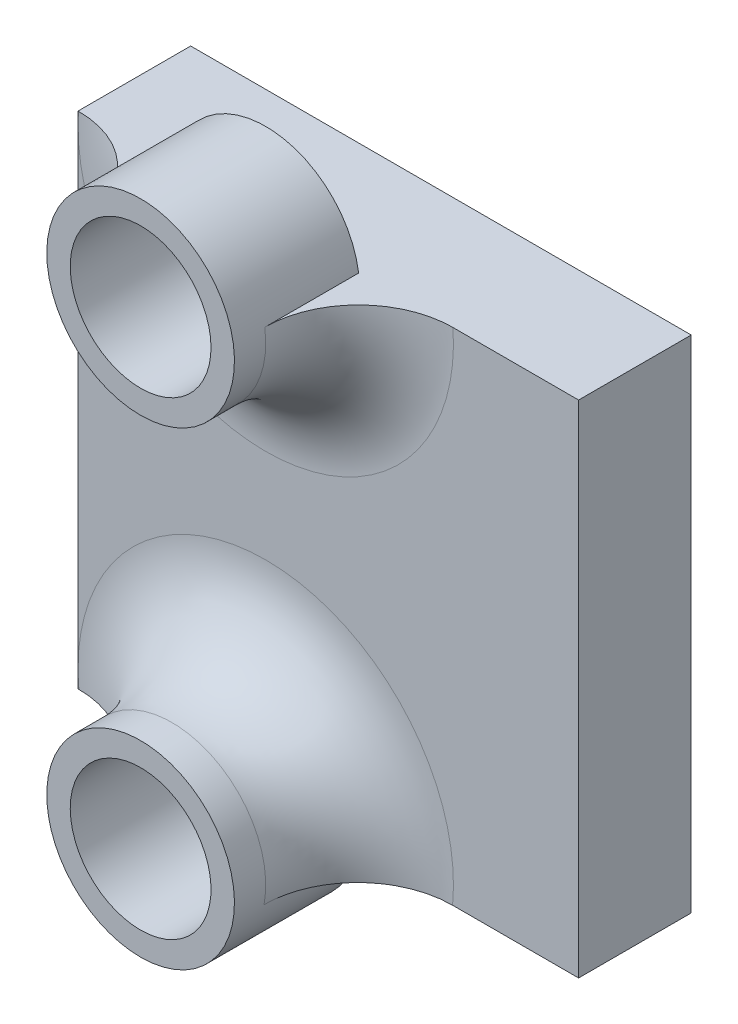
SolidWorks part; units mm, degrees
ref_plane "Front Plane" through (0, 0, 0) normal (0, 0, 1) x (1, 0, 0)
ref_plane "Top Plane" through (0, 0, 0) normal (0, 1, 0) x (1, 0, 0)
ref_plane "Right Plane" through (0, 0, 0) normal (1, 0, 0) x (0, 0, -1)
sketch "Sketch5" plane through (0, 0, 9.6) normal (0, 0, 1) x (1, 0, 0)
  line L0 (-72, -8) -> (-56, -8)
  line L1 (-72, -8) -> (-72, -24)
  line L2 (-56, -8) -> (-56, -24)
  line L4 (-72, -24) -> (-56, -24)
  line L5 (-56, -24) -> (-56, 8)
  line L6 (-56, 8) -> (-72, 8)
  line L7 (-72, 8) -> (-72, -24)
  line L8 (-72, -24) -> (-56, -24)
  arc A0 (-67.55, -23.425) -> (-64.45, -23.425) centre (-66, -23.425) ccw construction
  arc A1 (-67.55, -8.425) -> (-64.45, -8.425) centre (-66, -8.425) ccw construction
  arc A2 (-67.55, -23.425) -> (-64.45, -23.425) centre (-66, -23.425) ccw construction
  arc A3 (-67.55, -8.425) -> (-64.45, -8.425) centre (-66, -8.425) ccw construction
  circle A4 centre (-66, -8.425) radius 2.25
  circle A5 centre (-66, -23.425) radius 2.25
  circle A12 centre (-60, -12) radius 2.4 construction
  circle A13 centre (-60, -20) radius 2.4 construction
  circle A14 centre (-68, -20) radius 2.4 construction
  circle A15 centre (-68, -12) radius 2.4 construction
  circle A16 centre (-60, -12) radius 2.4 construction
  circle A17 centre (-60, -20) radius 2.4 construction
  circle A18 centre (-68, -20) radius 2.4 construction
  circle A19 centre (-68, -12) radius 2.4 construction
  circle A20 centre (-68, -12) radius 2.25
  circle A21 centre (-60, -12) radius 2.25
  circle A22 centre (-60, -20) radius 2.25
  circle A23 centre (-68, -20) radius 2.25
  circle A24 centre (-68, -20) radius 2.55
  circle A25 centre (-68, -12) radius 2.55
  circle A26 centre (-60, -12) radius 2.55
  circle A27 centre (-60, -20) radius 2.55
  circle A28 centre (-66, -8.425) radius 3
  circle A29 centre (-66, -23.425) radius 3
  line M6 (-72, -24) -> (-56, -24)
  line M7 (-56, -24) -> (-56, 8)
  line M9 (-72, 8) -> (-72, -24)
  circle M13 centre (-68, -4) radius 2.4
  circle M15 centre (-68, -12) radius 2.4
  circle M17 centre (-68, -20) radius 2.4
  dimension "D2" = 4.5
  dimension "D3" = 0.15
  dimension "D4" = 0.15
  dimension "D5" = 6
  dimension "D6" = 16
  dimension "D1" = 0
extrude "Boss-Extrude1" add sketch "Sketch5" along normal offset from surface (1.75 mm away) 0.15 contours A25 A4 L0 A5 A24 A27 A26 M9 M6 M7 | A25 A4 L0 | A24 A5 L8 | A29 A24 A5 M6 | A24 A29 L8 A5 | L0 A28 A25 A4 | A25 A28 L0 A4 region at (-63.7043, -15.9859, 9.6) region at (-68.5715, -8.7554, 9.6) region at (-65.8731, -9.0282, 9.6) region at (-64.0992, -9.8334, 9.6) region at (-68.5871, -23.244, 9.6) region at (-65.8433, -22.9295, 9.6) region at (-64.0554, -22.099, 9.6) offset beyond the face yes
extrude "Boss-Extrude2" add sketch "Sketch5<4>" along normal offset from surface (1.85 mm away) 4 from surface contours L1 L8 L2 L0 starting at face at (-60, -22.55, 11.35)
sketch "Sketch5<4>" plane through (0, 0, 9.6) normal (0, 0, 1) x (1, 0, 0) same geometry as "Sketch5"
extrude "Boss-Extrude3" add sketch "Sketch5<5>" along normal up to surface (4 mm away) from surface contours L8 A29 A5 M6 | A24 A29 L8 A5 | A23 A29 A5 | A29 A24 A5 M6 | A29 A24 A5 M17 | A23 A29 A5 M17 | A29 A23 A5 M17 | A24 A29 A5 M17 | A25 A28 L0 A4 | L0 A28 A4 M13 | L0 A28 A25 A4 | A28 M13 | A20 A28 A4 | A20 A28 A4 M15 | A28 A25 A4 M15 | A28 A20 A4 M15 | A25 A28 A4 M15 region at (-68.6512, -7.1653, 9.6) region at (-68.5715, -8.7554, 9.6) region at (-67.1261, -5.9335, 9.6) region at (-68.3553, -9.5617, 9.6) region at (-68.5871, -23.244, 9.6) region at (-68.5598, -24.0637, 9.6) region at (-64.0992, -9.8334, 9.6) region at (-68.2753, -9.7041, 9.6) region at (-68.4216, -22.4284, 9.6) region at (-64.0554, -22.099, 9.6) region at (-65.7362, -11.0269, 9.6) region at (-67.239, -10.6396, 9.6) region at (-68.3542, -22.2861, 9.6) region at (-65.8995, -11.0333, 9.6) region at (-65.6779, -20.8262, 9.6) region at (-67.2677, -21.2541, 9.6) region at (-65.8349, -20.815, 9.6) starting at face at (-64, -16, 13.2)
sketch "Sketch5<5>" plane through (0, 0, 9.6) normal (0, 0, 1) x (1, 0, 0) same geometry as "Sketch5"
fillet "Fillet1" radius 3 2 edges at (-66, -20.425, 13.2) (-66, -11.425, 13.2)
